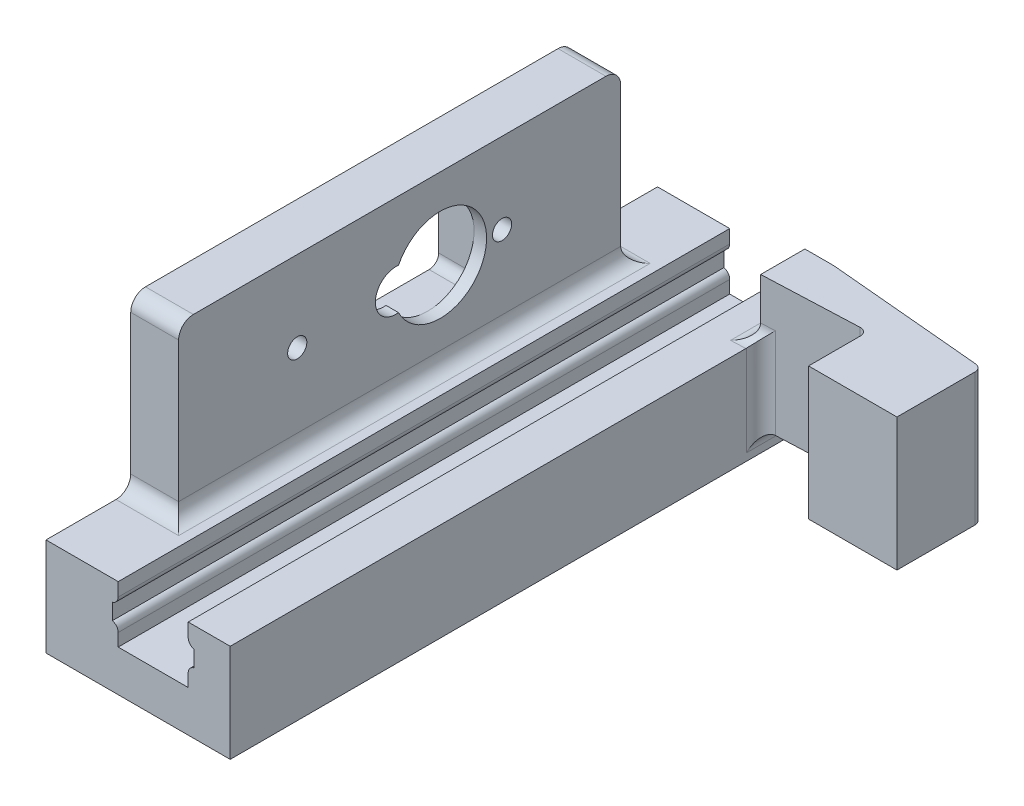
SolidWorks part; units mm, degrees
ref_plane "Front Plane" through (0, 0, 0) normal (0, 0, 1) x (1, 0, 0)
ref_plane "Top Plane" through (0, 0, 0) normal (0, 1, 0) x (1, 0, 0)
ref_plane "Right Plane" through (0, 0, 0) normal (1, 0, 0) x (0, 0, -1)
sketch "Sketch1" plane through (0, 0, 0) normal (0, 0, 1) x (1, 0, 0)
  line L1 (-2.5, -14.25) -> (2.5, -14.25)
  line L2 (-2.5, -14.25) -> (-2.5, 14.25)
  line L3 (-2.5, 14.25) -> (2.5, 14.25)
  line L4 (2.5, -14.25) -> (2.5, 14.25)
  line L5 (-2.5, -14.25) -> (2.5, 14.25) construction
  line L6 (-2.5, 14.25) -> (2.5, -14.25) construction
  point P0 (0, 0)
  dimension "D1" = 28.5
  dimension "D2" = 5
extrude "Boss-Extrude1" add sketch "Sketch1" along normal blind 5
sketch "Sketch2" plane through (0, 0, 5) normal (0, 0, 1) x (1, 0, 0)
  line L0 (-2.5, 14.25) -> (-2.5, -14.25) construction
  line L1 (-2.5, -6.05) -> (2.5, -6.05)
  line L2 (-2.5, -6.05) -> (-2.5, -14.25)
  line L3 (-2.5, -14.25) -> (2.5, -14.25)
  line L4 (2.5, -6.05) -> (2.5, -14.25)
  dimension "D1" = 8.2
extrude "Boss-Extrude2" add sketch "Sketch2" along normal blind 25
sketch "Sketch3" plane through (0, 0, 0) normal (0, 0, -1) x (-1, 0, 0)
  line L4 (2.5, -14.25) -> (2.5, -6.05)
  line L5 (-2.5, -14.25) -> (2.5, -14.25)
  line L6 (-2.5, -6.05) -> (-2.5, -14.25)
  line L7 (2.5, -6.05) -> (-2.5, -6.05)
  line L8 (2.5, -14.25) -> (2.5, -6.05)
  line L9 (-2.5, -14.25) -> (2.5, -14.25)
  line L10 (-2.5, -6.05) -> (-2.5, -14.25)
  line L11 (2.5, -6.05) -> (-2.5, -6.05)
  dimension "D1" = 0
extrude "Boss-Extrude3" add sketch "Sketch3" along normal blind 53
sketch "Sketch4" plane through (0, -6.05, 0) normal (0, 1, 0) x (1, 0, 0)
  line L5 (-2.5, 53) -> (-2.5, 0) construction
  line L6 (-2.5, 28) -> (2.5, 28)
  line L7 (-2.5, 28) -> (-2.5, 23)
  line L8 (-2.5, 23) -> (2.5, 23)
  line L9 (2.5, 28) -> (2.5, 23)
  line L10 (2.5, 53) -> (2.5, 0) construction
  line L11 (-2.5, 53) -> (2.5, 53) construction
  dimension "D1" = 5
  dimension "D2" = 25
extrude "Boss-Extrude4" add sketch "Sketch4" along normal blind 20.3
sketch "Sketch5" plane through (2.5, 0, 0) normal (1, 0, 0) x (0, 0, -1)
  line L1 (-30, -6.05) -> (53, -6.05)
  line L2 (-30, -6.05) -> (-30, -14.25)
  line L3 (-30, -14.25) -> (53, -14.25)
  line L4 (53, -6.05) -> (53, -14.25)
extrude "Boss-Extrude5" add sketch "Sketch5" along normal blind 20
sketch "Sketch7" plane through (0, -6.05, 0) normal (0, 1, 0) x (1, 0, 0)
  line L5 (22.5, 53) -> (-2.5, 53) construction
  line L6 (16.8, 53) -> (7.3, 53)
  line L7 (16.8, 53) -> (16.8, -30)
  line L8 (16.8, -30) -> (7.3, -30)
  line L9 (7.3, 53) -> (7.3, -30)
  line L11 (22.5, 53) -> (22.5, -30) construction
  dimension "D1" = 83
  dimension "D2" = 9.5
  dimension "D3" = 15.2
extrude "Cut-Extrude1" cut sketch "Sketch7" against normal blind 4.6 and the other way through all
sketch "Sketch9" plane through (0, -6.05, 0) normal (0, 1, 0) x (1, 0, 0)
  line L18 (7.3, -30) -> (7.3, 53)
  line L19 (7.3, 53) -> (-2.5, 53)
  line L20 (-2.5, 53) -> (-2.5, 28)
  line L21 (-2.5, 28) -> (2.5, 28)
  line L22 (2.5, 28) -> (2.5, 23)
  line L23 (2.5, 23) -> (-2.5, 23)
  line L24 (-2.5, 23) -> (-2.5, 0)
  line L25 (-2.5, 0) -> (2.5, 0)
  line L26 (2.5, 0) -> (2.5, -5)
  line L27 (2.5, -5) -> (-2.5, -5)
  line L28 (-2.5, -5) -> (-2.5, -30)
  line L29 (-2.5, -30) -> (7.3, -30)
  line L34 (7.3, -30) -> (7.3, 53)
  line L35 (7.3, 53) -> (-2.5, 53)
  line L36 (-2.5, 53) -> (-2.5, 28)
  line L37 (-2.5, 28) -> (2.5, 28)
  line L38 (2.5, 28) -> (2.5, 23)
  line L39 (2.5, 23) -> (-2.5, 23)
  line L40 (-2.5, 23) -> (-2.5, 0)
  line L41 (-2.5, 0) -> (2.5, 0)
  line L42 (2.5, 0) -> (2.5, -5)
  line L43 (2.5, -5) -> (-2.5, -5)
  line L44 (-2.5, -5) -> (-2.5, -30)
  line L45 (-2.5, -30) -> (7.3, -30)
  dimension "D1" = 0
extrude "Boss-Extrude6" add sketch "Sketch9" along normal blind 2.1
sketch "Sketch17" plane through (0, -14.25, 0) normal (0, -1, 0) x (1, 0, 0)
  line L0 (22.5, -48) -> (22.5, -42)
  line L1 (22.5, 30) -> (22.5, -53) construction
  line L2 (22.5, -42) -> (35.4623, -42.5401)
  line L5 (48.5, -34.5) -> (48.5, -45.0866)
  line L6 (47.5903, -46.0825) -> (26.4951, -47.9959)
  line L7 (26.4047, -48) -> (22.5, -48)
  line L9 (48.5, -34.5) -> (36.5, -34.5)
  line L10 (36.5, -34.5) -> (36.5, -41.4523)
  arc A0 (35.4623, -42.5401) -> (36.5, -41.4523) centre (35.5039, -41.541) ccw
  arc A3 (48.5, -45.0866) -> (47.5903, -46.0825) centre (47.5, -45.0866) cw
  arc A4 (26.4951, -47.9959) -> (26.4047, -48) centre (26.4047, -47) cw
  point P11 (34.3752, -42.4948)
  point P14 (34.4288, -36.495)
  point P17 (48.4186, -36.0003)
  point P20 (48.5, -46)
  point P23 (26.45, -48)
  dimension "D8" = 1
  dimension "D1" = 6
  dimension "D2" = 3.95
  dimension "D3" = 26
  dimension "D4" = 2
  dimension "D5" = 10
  dimension "D6" = 12
  dimension "D7" = 6
  dimension "D9" = 5
extrude "Boss-Extrude9" add sketch "Sketch17" against normal blind 19
sketch "Sketch21" plane through (2.5, 0, 0) normal (1, 0, 0) x (0, 0, -1)
  circle A0 centre (-2.4, 9.0802) radius 1.3
  dimension "D1" = 2.6
extrude "Cut-Extrude4" cut sketch "Sketch21" against normal blind 16 and the other way through all
ref_plane "Plane1" through (0, 0, -11.5) normal (0, 0, 1) x (1, 0, 0)
mirror "Mirror1" about plane through (0, 0, -11.5) normal (0, 0, 1) of "Cut-Extrude4"
sketch "Sketch24" plane through (-2.5, 0, 0) normal (-1, 0, 0) x (0, 0, 1)
  line L0 (-53, -3.95) -> (-28, -3.95) construction
  line L1 (18.5, 20.05) -> (-41.5, 20.05)
  line L2 (18.5, 20.05) -> (18.5, -3.95)
  line L3 (18.5, -3.95) -> (-41.5, -3.95)
  line L4 (-41.5, 20.05) -> (-41.5, -3.95)
  line L6 (5, -3.95) -> (5, 14.25)
  line L7 (5, 14.25) -> (0, 14.25)
  line L8 (0, 14.25) -> (0, -3.95)
  line L13 (-23, -3.95) -> (-23, 14.25)
  line L14 (-28, -3.95) -> (-23, -3.95)
  line L15 (-28, 14.25) -> (-28, -3.95)
  line L16 (-23, 14.25) -> (-28, 14.25)
  line L17 (-23, -3.95) -> (-23, 14.25)
  line L18 (-28, -3.95) -> (-23, -3.95)
  line L19 (-28, 14.25) -> (-28, -3.95)
  line L20 (-23, 14.25) -> (-28, 14.25)
  circle A0 centre (2.4, 9.0802) radius 1.3 construction
  circle A1 centre (2.4, 9.0802) radius 1.3
  circle A2 centre (-25.4, 9.0802) radius 1.3 construction
  circle A3 centre (-25.4, 9.0802) radius 1.3
  line M9 (0, 14.25) -> (0, -3.95)
  line M10 (0, -3.95) -> (-23, -3.95)
  line M11 (-23, -3.95) -> (-23, 14.25)
  line M12 (-23, 14.25) -> (-28, 14.25)
  line M13 (-28, 14.25) -> (-28, -3.95)
  line M14 (-28, -3.95) -> (-53, -3.95)
  line M18 (30, -3.95) -> (5, -3.95)
  line M19 (5, -3.95) -> (5, 14.25)
  line M20 (5, 14.25) -> (0, 14.25)
  dimension "D1" = 24
  dimension "D2" = 60
  dimension "D3" = 11.5
  dimension "D4" = 0
extrude "Boss-Extrude10" add sketch "Sketch24" against normal blind 6.5 contours L1 L4 L2 M14 M13 M12 M11 M10 M9 M20 M19 M18 region at (-2.5, 8.4696, -11.5)
sketch "Sketch25" plane through (2.5, 0, 0) normal (1, 0, 0) x (0, 0, -1)
  line L4 (-5, 14.25) -> (-5, -3.95)
  line L5 (-5, -3.95) -> (0, -3.95)
  line L6 (0, -3.95) -> (0, 14.25)
  line L7 (0, 14.25) -> (-5, 14.25)
  line L8 (-5, 14.25) -> (-5, -3.95)
  line L9 (-5, -3.95) -> (0, -3.95)
  line L10 (0, -3.95) -> (0, 14.25)
  line L11 (0, 14.25) -> (-5, 14.25)
  line L12 (23, 14.25) -> (23, -3.95)
  line L13 (23, -3.95) -> (28, -3.95)
  line L14 (28, -3.95) -> (28, 14.25)
  line L15 (28, 14.25) -> (23, 14.25)
  line L16 (23, 14.25) -> (23, -3.95)
  line L17 (23, -3.95) -> (28, -3.95)
  line L18 (28, -3.95) -> (28, 14.25)
  line L19 (28, 14.25) -> (23, 14.25)
  circle A0 centre (-2.4, 9.0802) radius 1.3 construction
  circle A1 centre (-2.4, 9.0802) radius 1.3
  circle A2 centre (25.4, 9.0802) radius 1.3 construction
  circle A3 centre (25.4, 9.0802) radius 1.3
  dimension "D1" = 0
  dimension "D2" = 0
extrude "Boss-Extrude11" add sketch "Sketch25" along normal up to surface (1.5 mm away) up to face at (4, 6.1167, -11.5)
sketch "Sketch26" plane through (4, 0, 0) normal (1, 0, 0) x (0, 0, -1)
  arc A4 (11.3458, 6.3479) -> (11.3458, 11.905) centre (17, 9.1264) ccw
  arc A5 (11.3458, 11.905) -> (11.3458, 6.3479) centre (11, 9.1264) ccw
  dimension "D2" = 12.6
extrude "Cut-Extrude5" cut sketch "Sketch26" against normal through all
sketch "Sketch30" plane through (-2.5, 0, 0) normal (-1, 0, 0) x (0, 0, 1)
  line L47 (0.3, 4.1264) -> (0.3, 14.1264)
  line L48 (-1, 15.4264) -> (-17, 15.4264)
  line L49 (-17, 15.4264) -> (-22, 15.4264)
  line L50 (-23.3, 14.1264) -> (-23.3, 9.1264)
  line L51 (-23.3, 9.1264) -> (-23.3, 4.1264)
  line L52 (-22, 2.8264) -> (-17, 2.8264)
  line L53 (-17, 2.8264) -> (-1, 2.8264)
  arc A27 (0.3, 14.1264) -> (-1, 15.4264) centre (-1, 14.1264) ccw
  arc A28 (-22, 15.4264) -> (-23.3, 14.1264) centre (-22, 14.1264) ccw
  arc A29 (-23.3, 4.1264) -> (-22, 2.8264) centre (-22, 4.1264) ccw
  arc A30 (-1, 2.8264) -> (0.3, 4.1264) centre (-1, 4.1264) ccw
  point P0 (0, 0)
extrude "Cut-Extrude7" cut sketch "Sketch30" against normal blind 4.8
sketch "Sketch31" plane through (0, -6.05, 0) normal (0, 1, 0) x (1, 0, 0)
  line L7 (16.8, 53) -> (16.8, -30)
  line L8 (16.8, -30) -> (22.5, -30)
  line L9 (22.5, -30) -> (22.5, 42)
  line L10 (22.5, 42) -> (22.5, 48)
  line L11 (22.5, 48) -> (22.5, 53)
  line L12 (22.5, 53) -> (16.8, 53)
  line L14 (16.8, 53) -> (16.8, -30)
  line L15 (16.8, -30) -> (22.5, -30)
  line L16 (22.5, -30) -> (22.5, 42)
  line L17 (22.5, 42) -> (22.5, 48)
  line L18 (22.5, 48) -> (22.5, 53)
  line L19 (22.5, 53) -> (16.8, 53)
  dimension "D1" = 0
extrude "Boss-Extrude12" add sketch "Sketch31" along normal blind 2.1
sketch "Sketch32" plane through (16.8, 0, 0) normal (-1, 0, 0) x (0, 0, 1)
  line L0 (-53, -14.25) -> (-53, -3.95) construction
  line L1 (-53, -5.75) -> (30, -5.75)
  line L2 (-53, -5.75) -> (-53, -7.95)
  line L3 (-53, -7.95) -> (30, -7.95)
  line L4 (30, -5.75) -> (30, -7.95)
  line L5 (30, -3.95) -> (30, -14.25) construction
  line L6 (30, -10.65) -> (-53, -10.65) construction
  dimension "D1" = 2.2
  dimension "D2" = 2.7
extrude "Cut-Extrude8" cut sketch "Sketch32" against normal blind 0.8 and the other way blind 10.3
sketch "Sketch33" plane through (0, -14.25, 0) normal (0, -1, 0) x (1, 0, 0)
  line L11 (-2.5, 30) -> (-2.5, -53)
  line L12 (-2.5, -53) -> (22.5, -53)
  line L13 (22.5, -53) -> (22.5, -48)
  line L14 (22.5, -48) -> (26.4047, -48)
  line L15 (26.4951, -47.9959) -> (47.5903, -46.0825)
  line L16 (48.5, -45.0866) -> (48.5, -34.5)
  line L17 (48.5, -34.5) -> (36.5, -34.5)
  line L18 (36.5, -34.5) -> (36.5, -41.4523)
  line L19 (35.4623, -42.5401) -> (22.5, -42)
  line L20 (22.5, -42) -> (22.5, 30)
  line L21 (22.5, 30) -> (-2.5, 30)
  line L22 (-2.5, 30) -> (-2.5, -53)
  line L23 (-2.5, -53) -> (22.5, -53)
  line L24 (22.5, -53) -> (22.5, -48)
  line L25 (22.5, -48) -> (26.4047, -48)
  line L26 (26.4951, -47.9959) -> (47.5903, -46.0825)
  line L27 (48.5, -45.0866) -> (48.5, -34.5)
  line L28 (48.5, -34.5) -> (36.5, -34.5)
  line L29 (36.5, -34.5) -> (36.5, -41.4523)
  line L30 (35.4623, -42.5401) -> (22.5, -42)
  line L31 (22.5, -42) -> (22.5, 30)
  line L32 (22.5, 30) -> (-2.5, 30)
  arc A6 (26.4047, -48) -> (26.4951, -47.9959) centre (26.4047, -47) ccw
  arc A7 (47.5903, -46.0825) -> (48.5, -45.0866) centre (47.5, -45.0866) ccw
  arc A8 (35.4623, -42.5401) -> (36.5, -41.4523) centre (35.5039, -41.541) ccw
  arc A11 (26.4047, -48) -> (26.4951, -47.9959) centre (26.4047, -47) ccw
  arc A12 (47.5903, -46.0825) -> (48.5, -45.0866) centre (47.5, -45.0866) ccw
  arc A13 (35.4623, -42.5401) -> (36.5, -41.4523) centre (35.5039, -41.541) ccw
  dimension "D1" = 0
extrude "Cut-Extrude9" cut sketch "Sketch33" against normal blind 1
sketch "Sketch34" plane through (0, -3.95, 0) normal (0, 1, 0) x (1, 0, 0)
  line L6 (16.8, -30) -> (22.5, -30)
  line L7 (22.5, -30) -> (22.5, 42)
  line L8 (-2.5, 41.5) -> (4, 41.5)
  line L9 (4, 41.5) -> (4, -18.5)
  line L10 (4, -18.5) -> (-2.5, -18.5)
  line L11 (-2.5, -18.5) -> (-2.5, -30)
  line L12 (-2.5, -30) -> (7.3, -30)
  line L13 (7.3, -30) -> (7.3, 53)
  line L14 (7.3, 53) -> (-2.5, 53)
  line L15 (-2.5, 53) -> (-2.5, 41.5)
  line L16 (-2.5, 41.5) -> (4, 41.5)
  line L17 (4, 41.5) -> (4, -18.5)
  line L18 (4, -18.5) -> (-2.5, -18.5)
  line L19 (-2.5, -18.5) -> (-2.5, -30)
  line L20 (-2.5, -30) -> (7.3, -30)
  line L21 (7.3, -30) -> (7.3, 53)
  line L22 (7.3, 53) -> (-2.5, 53)
  line L23 (-2.5, 53) -> (-2.5, 41.5)
  line L24 (22.5, 42) -> (22.5, 48)
  line L25 (22.5, 48) -> (22.5, 53)
  line L26 (22.5, 53) -> (16.8, 53)
  line L27 (16.8, 53) -> (16.8, -30)
  line L28 (16.8, -30) -> (22.5, -30)
  line L29 (22.5, -30) -> (22.5, 42)
  line L30 (22.5, 42) -> (22.5, 48)
  line L31 (22.5, 48) -> (22.5, 53)
  line L32 (22.5, 53) -> (16.8, 53)
  line L33 (16.8, 53) -> (16.8, -30)
  dimension "D1" = 0
  dimension "D2" = 0
extrude "Boss-Extrude13" add sketch "Sketch34" along normal blind 1
fillet "Fillet6" radius 2 5 edges at (0.75, 20.05, -41.5) (0.75, 20.05, 18.5) (0.75, -2.95, 18.5) (4, -2.95, -11.5) (0.75, -2.95, -41.5)
fillet "Fillet7" radius 1 4 edges at (7.3, -7.95, -11.5) (7.3, -5.75, -11.5) (16.8, -7.95, -11.5) (16.8, -5.75, -11.5)
fillet "Fillet8" radius 2 2 edges at (22.5, -8.1, -42) (22.5, -8.1, -48)
fillet "Fillet9" radius 2 1 edges at (22.5, -2.95, -45)
fillet "Fillet10" radius 2 2 edges at (22.4584, -2.95, -41.9983) (22.5, -2.95, -48)
sketch "Sketch35" plane through (0, -13.25, 0) normal (0, -1, 0) x (1, 0, 0)
  line L1 (-2.5, 30) -> (22.5, 30)
  line L2 (-2.5, 30) -> (-2.5, -53)
  line L3 (-2.5, -53) -> (22.5, -53)
  line L4 (22.5, 30) -> (22.5, -53)
extrude "Boss-Extrude14" add sketch "Sketch35" along normal blind 3
fillet "Fillet11" radius 2 1 edges at (22.5, -13.25, -45.0408)
